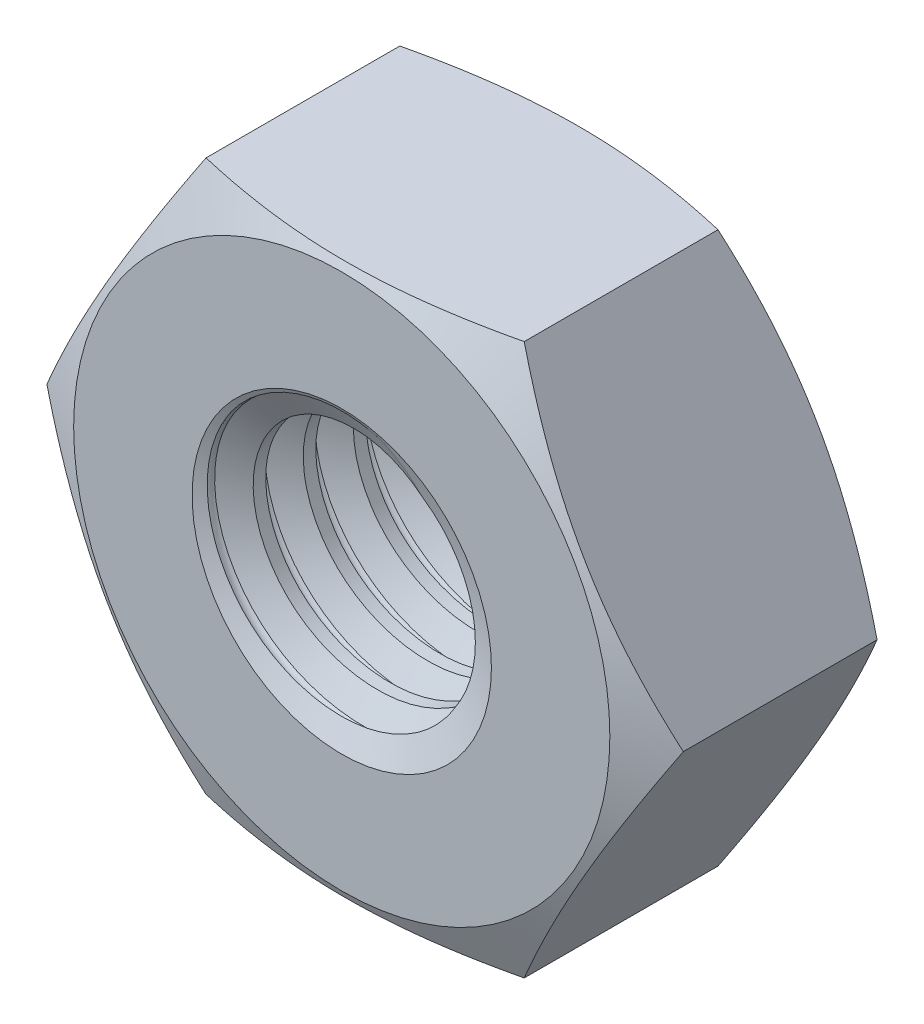
SolidWorks part; units mm, degrees
material "Stainless Steel (ferritic)"
ref_plane "Ebene vorne" through (0, 0, 0) normal (0, 0, 1) x (1, 0, 0)
ref_plane "Ebene oben" through (0, 0, 0) normal (0, 1, 0) x (1, 0, 0)
ref_plane "Ebene rechts" through (0, 0, 0) normal (1, 0, 0) x (0, 0, -1)
sketch "Sketch1" plane through (0, 0, 0) normal (0, 0, 1) x (1, 0, 0)
  line L0 (-1.5877, 2.75) -> (1.5877, 2.75)
  line L1 (1.5877, 2.75) -> (3.1754, 0)
  line L2 (3.1754, 0) -> (1.5877, -2.75)
  line L3 (1.5877, -2.75) -> (-1.5877, -2.75)
  line L4 (-1.5877, -2.75) -> (-3.1754, 0)
  line L5 (-3.1754, 0) -> (-1.5877, 2.75)
  circle A0 centre (0, 0) radius 1.1935
  circle A1 centre (0, 0) radius 3.1754
  dimension "D1" = 2.387
  dimension "D2" = 5.5
  dimension "D3" = 120
extrude "Boss-Extrude2" add sketch "Sketch1" against normal blind 2.4 contours L5 L4 L3 L2 L1 L0 A0 | L5 A1 | L0 A1 | L1 A1 | L2 A1 | L4 A1 | L3 A1 region at (0, 2.9212, 0) region at (0, 2.666, 0) region at (-2.5298, 1.4606, 0) region at (2.5298, 1.4606, 0) region at (-2.5298, -1.4606, 0) region at (2.5298, -1.4606, 0) region at (0, -2.9212, 0)
chamfer "Chamfer1" distance 0.5 angle 25 1 edges at (3.1754, 0, -2.4) first distance on face at (1.1935, 0, -2.4)
chamfer "Chamfer2" distance 0.5 angle 25 1 edges at (3.1754, 0, 0) first distance on face at (1.1935, 0, 0)
extrude "Cut-Extrude1" cut sketch "Sketch1<4>" against normal blind 2.4 flip side to cut contours L0 L1 L2 L3 L4 L5
sketch "Sketch1<4>" plane through (0, 0, 0) normal (0, 0, 1) x (1, 0, 0) same geometry as "Sketch1"
sketch "Sketch6" plane through (0, 0, 0) normal (1, 0, 0) x (0, 0, -1)
  line L0 (-2.0885, 0) -> (5.2282, 0) construction
  line L1 (-1.25, 1.8226) -> (-1.25, -0.8762) construction
  line L2 (-1, 1.8226) -> (-1, -0.8768) construction
  line L3 (-1.5, 1.8226) -> (-1.5, -0.8762) construction
  line L4 (-1.2264, 1.1935) -> (3.6307, 1.1935) construction
  line L5 (-1.1875, 1.1935) -> (-1.0465, 1.4376)
  line L6 (-0.75, 1.8226) -> (-0.75, -0.8768) construction
  line L7 (-0.9535, 1.4376) -> (-0.8125, 1.1935)
  line L8 (-1.25, 1.0852) -> (-1, 1.5183) construction
  line L9 (-1, 1.5183) -> (-0.75, 1.0852) construction
  line L10 (-1.1875, 1.1935) -> (-0.8125, 1.1935)
  arc A0 (-1.0465, 1.4376) -> (-0.9535, 1.4376) centre (-1, 1.3952) cw
  point P16 (-2.3334, 2.061)
  point P18 (-0.6964, 1.591)
  dimension "D8" = 0.063
  dimension "D1" = 0.25
  dimension "D2" = 0.25
  dimension "D3" = 1.1935
  dimension "D4" = 1
  dimension "D5" = 0.25
  dimension "D6" = 60
  dimension "D7" = 0.1082
ref_plane "Plane2" through (0, 0, 1) normal (0, 0, 1) x (1, 0, 0)
sketch "Sketch7" plane through (0, 0, 1) normal (0, 0, 1) x (1, 0, 0)
  circle A0 centre (0, 0) radius 1.1935
curve "Helix/Spiral2" pitch 0.5 height 4 radius 1.1935 left hand yes centre (0, 0, 1) axis (0, 0, -1) start towards (0, 1, 0)
chamfer "Chamfer3" distance 0.3 angle 25 1 edges at (1.1935, 0, 0) first distance on face at (2.6754, 0, 0)
chamfer "Chamfer4" distance 0.3 angle 25 1 edges at (1.1935, 0, -2.4) first distance on face at (2.6754, 0, -2.4)
sweep "Cut-Sweep2" cut profiles "Sketch6" path "Helix/Spiral2" align with end faces yes
